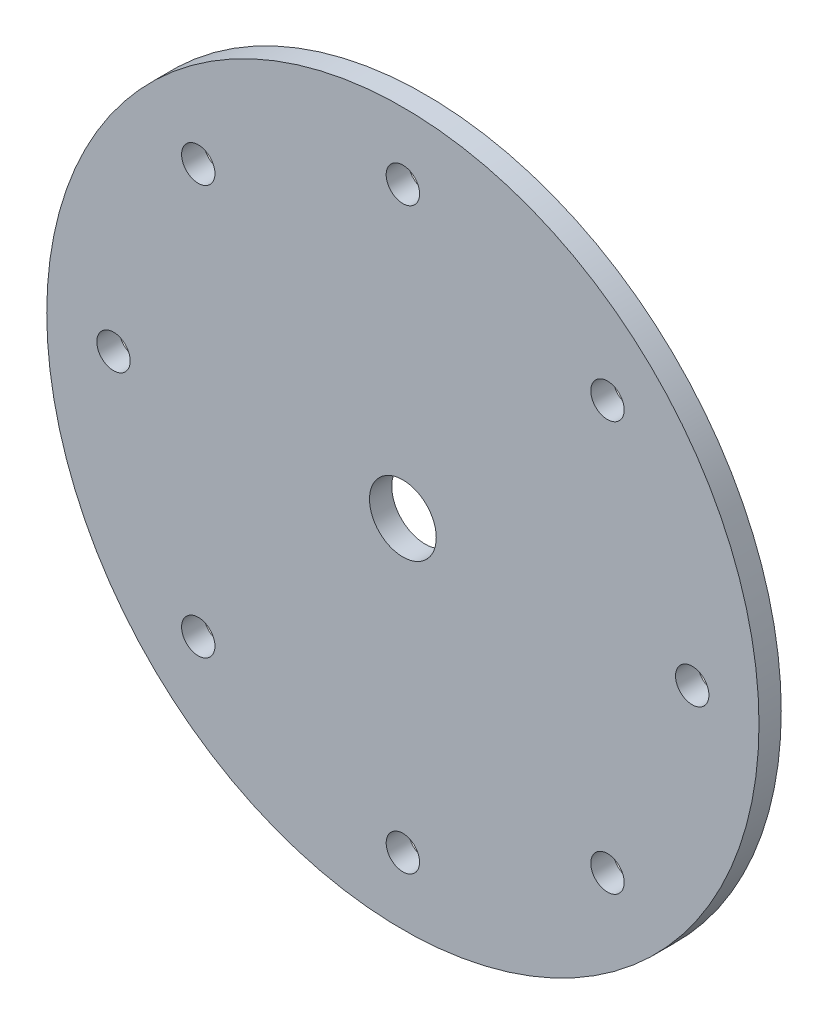
SolidWorks part; units mm, degrees
material "Plain Carbon Steel"
ref_plane "Front Plane" through (0, 0, 0) normal (0, 0, 1) x (1, 0, 0)
ref_plane "Top Plane" through (0, 0, 0) normal (0, 1, 0) x (1, 0, 0)
ref_plane "Right Plane" through (0, 0, 0) normal (1, 0, 0) x (0, 0, -1)
sketch "Sketch1" plane through (0, 0, 0) normal (0, 0, 1) x (1, 0, 0)
  line L0 (0, 101.6) -> (0, -101.6) construction
  line L1 (-101.6, 0) -> (101.6, 0) construction
  line L2 (-58.3717, 58.3717) -> (58.3717, -58.3717) construction
  line L3 (-58.3717, -58.3717) -> (58.3717, 58.3717) construction
  circle A0 centre (0, 0) radius 101.6
  circle A1 centre (0, 0) radius 9.525
  circle A2 centre (0, 82.55) radius 4.7625
  circle A6 centre (58.3717, 58.3717) radius 4.7625
  circle A7 centre (82.55, 0) radius 4.7625
  circle A8 centre (58.3717, -58.3717) radius 4.7625
  circle A9 centre (0, -82.55) radius 4.7625
  circle A10 centre (-58.3717, -58.3717) radius 4.7625
  circle A11 centre (-82.55, 0) radius 4.7625
  circle A12 centre (-58.3717, 58.3717) radius 4.7625
  dimension "D1" = 203.2
  dimension "D2" = 19.05
  dimension "D3" = 9.525
  dimension "D6" = 19.05
  dimension "D4" = 19.05
  dimension "D5" = 8
extrude "Rotor Disc" add sketch "Sketch1" along normal blind 6.35 contours A0 A12 A11 A10 A8 A7 A6 A1 A2 region at (-98.7263, 0, 0)
